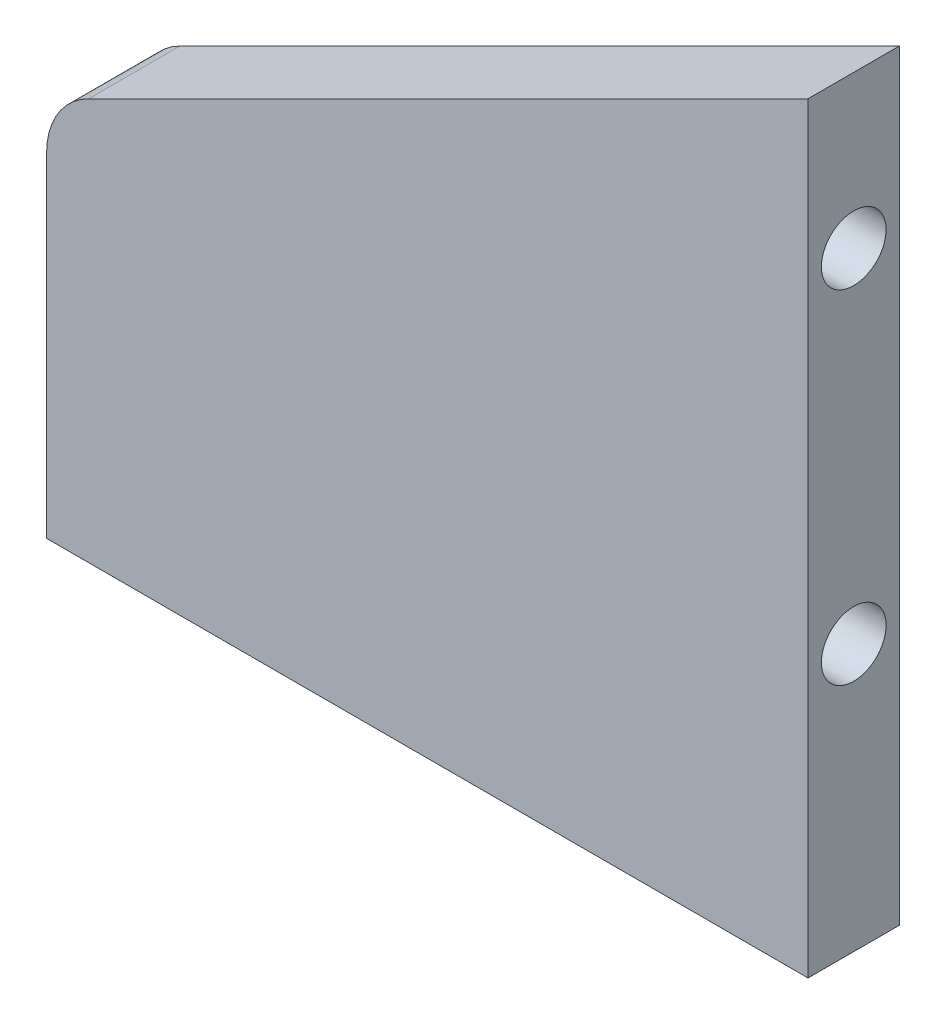
SolidWorks part; units mm, degrees
ref_plane "Vorne" through (0, 0, 0) normal (0, 0, 1) x (1, 0, 0)
ref_plane "Oben" through (0, 0, 0) normal (0, 1, 0) x (1, 0, 0)
ref_plane "Rechts" through (0, 0, 0) normal (1, 0, 0) x (0, 0, -1)
ref_plane "E_Boden" through (0, 1, 0) normal (0, 1, 0) x (1, 0, 0)
sketch "Skizze1" plane through (0, 0, 0) normal (0, 0, 1) x (1, 0, 0)
  line L0 (0, 10) -> (0, -9.5229) construction
  line L1 (-15.5467, 0) -> (14.4334, 0) construction
  line L2 (100, 0) -> (100, 100)
  line L4 (0, 0) -> (100, 0)
  line L5 (0, 0) -> (0, 50)
  line L6 (0, 50) -> (100, 100)
  dimension "D1" = 100
  dimension "D2" = 100
  dimension "D3" = 50
extrude "Aufsatz-Linear austragen1" add sketch "Skizze1" along normal blind 12
fillet "Verrundung1" radius 10 1 edges at (0, 50, 6)
hole_wizard "M10 Gewindebohrung1" positions "Skizze2" profile "Skizze3" tap size "M10" standard "DIN"
sketch "Skizze2" plane through (0, 0, 0) normal (0, -1, 0) x (-1, 0, 0)
  line L0 (-100, -6) -> (0, -6) construction
  line L1 (-100, -12) -> (-100, 0) construction
  line L2 (0, -12) -> (0, 0) construction
  line L4 (-50, 0) -> (-50, -12) construction
  line L5 (0, 0) -> (-100, 0) construction
  line L6 (0, -12) -> (-100, -12) construction
  point P0 (-85, -6)
  point P17 (-85, -6)
  dimension "D1" = 15
sketch "Skizze3" plane through (85, 0, 6) normal (1, 0, 0) x (0, 0, -1)
  line L0 (0, 0) -> (0, 30.0537)
  line L1 (0, 30.0537) -> (4.25, 27.5)
  line L2 (4.25, 27.5) -> (4.25, 0)
  line L5 (4.25, 0) -> (0, 0)
  line L10 (0, 30.0537) -> (-4.25, 27.5) construction
  line L11 (0, -6.35) -> (0, 107.95) construction
  dimension "Bohrerdurchmesser" = 8.5
  dimension "Bohrungstiefe" = 27.5
  dimension "Spitzenwinkel" = 118
cosmetic thread "Bohrungsgewinde1" parameters "D1"=20, "D2"=10
hole_wizard "M10 Gewindebohrung2" positions "Skizze4" profile "Skizze5" tap size "M10" standard "DIN"
sketch "Skizze4" plane through (0, 0, 0) normal (0, -1, 0) x (-1, 0, 0)
  line L0 (0, -6) -> (-100, -6) construction
  line L1 (0, -12) -> (0, 0) construction
  line L2 (-100, -12) -> (-100, 0) construction
  point P0 (-15, -6)
  point P11 (-23.5491, -6)
  dimension "D1" = 15
sketch "Skizze5" plane through (15, 0, 6) normal (1, 0, 0) x (0, 0, -1)
  line L0 (0, 0) -> (0, 30.0537)
  line L1 (0, 30.0537) -> (4.25, 27.5)
  line L2 (4.25, 27.5) -> (4.25, 0)
  line L5 (4.25, 0) -> (0, 0)
  line L10 (0, 30.0537) -> (-4.25, 27.5) construction
  line L11 (0, -6.35) -> (0, 107.95) construction
  dimension "Bohrerdurchmesser" = 8.5
  dimension "Bohrungstiefe" = 27.5
  dimension "Spitzenwinkel" = 118
cosmetic thread "Bohrungsgewinde2" parameters "D1"=20, "D2"=10
hole_wizard "M10 Gewindebohrung3" positions "Skizze6" profile "Skizze7" tap size "M10" standard "DIN"
sketch "Skizze6" plane through (100, 0, 0) normal (1, 0, 0) x (0, 0, -1)
  line L0 (-12, 0) -> (0, 0) construction
  line L1 (-6, 100) -> (-6, 0) construction
  line L2 (-12, 100) -> (0, 100) construction
  point P0 (-6, 35)
  point P10 (-6, 40)
  dimension "D1" = 35
sketch "Skizze7" plane through (100, 35, 6) normal (0, 1, 0) x (0, 0, -1)
  line L0 (0, 0) -> (0, 30.0537)
  line L1 (0, 30.0537) -> (4.25, 27.5)
  line L2 (4.25, 27.5) -> (4.25, 0)
  line L5 (4.25, 0) -> (0, 0)
  line L10 (0, 30.0537) -> (-4.25, 27.5) construction
  line L11 (0, -6.35) -> (0, 107.95) construction
  dimension "Bohrerdurchmesser" = 8.5
  dimension "Bohrungstiefe" = 27.5
  dimension "Spitzenwinkel" = 118
cosmetic thread "Bohrungsgewinde3" parameters "D1"=20, "D2"=10
hole_wizard "M10 Gewindebohrung4" positions "Skizze8" profile "Skizze9" tap size "M10" standard "DIN"
sketch "Skizze8" plane through (100, 0, 0) normal (1, 0, 0) x (0, 0, -1)
  line L0 (-6, 100) -> (-6, 0) construction
  line L1 (-12, 100) -> (0, 100) construction
  line L2 (-12, 0) -> (0, 0) construction
  point P0 (-6, 80)
  point P10 (-6, 79.2355)
  dimension "D1" = 20
sketch "Skizze9" plane through (100, 80, 6) normal (0, 1, 0) x (0, 0, -1)
  line L0 (0, 0) -> (0, 27.5537)
  line L1 (0, 27.5537) -> (4.25, 25)
  line L2 (4.25, 25) -> (4.25, 0)
  line L5 (4.25, 0) -> (0, 0)
  line L10 (0, 27.5537) -> (-4.25, 25) construction
  line L11 (0, -6.35) -> (0, 107.95) construction
  dimension "Bohrerdurchmesser" = 8.5
  dimension "Bohrungstiefe" = 25
  dimension "Spitzenwinkel" = 118
cosmetic thread "Bohrungsgewinde4" parameters "D1"=20, "D2"=10
